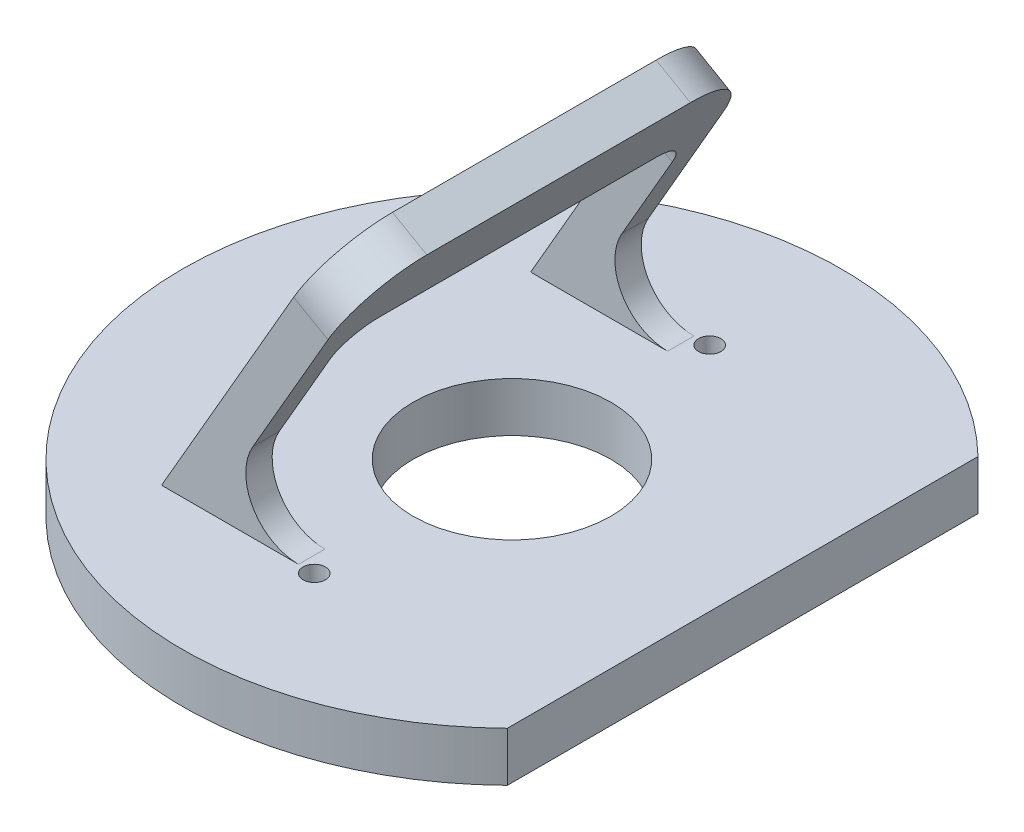
SolidWorks part; units mm, degrees
ref_plane "前视基准面" through (0, 0, 0) normal (0, 0, 1) x (1, 0, 0)
ref_plane "上视基准面" through (0, 0, 0) normal (0, 1, 0) x (1, 0, 0)
ref_plane "右视基准面" through (0, 0, 0) normal (1, 0, 0) x (0, 0, -1)
other "Configuration Table"
sketch "草图9" plane through (0, 0, 0) normal (0, 1, 0) x (1, 0, 0)
  line L0 (70, 71.4143) -> (70, -71.4143)
  arc A0 (70, 71.4143) -> (70, -71.4143) centre (0, 0) ccw
  circle A1 centre (0, 0) radius 30
  dimension "D1" = 200
  dimension "D2" = 60
  dimension "D3" = 70
extrude "凸台-拉伸3" add sketch "草图9" along normal blind 15
sketch "草图10" plane through (0, 0, 0) normal (0, 1, 0) x (1, 0, 0)
  line L0 (-55, 72.7753) -> (-55, -63.7573) construction
  dimension "D1" = 55
ref_plane "基准面1" through (-41.25, 23.8157, 0) normal (-0.866, 0.5, 0) x (0, 0, 1)
sketch "草图11" plane through (-41.25, 23.8157, 0) normal (-0.866, 0.5, 0) x (0, 0, 1)
  line L0 (-60, -9.9798) -> (-60, 70.0202)
  line L1 (0, -9.9798) -> (0, 116.3499) construction
  line L2 (-40, 90.0202) -> (40, 90.0202)
  line L3 (-52, -9.9798) -> (-52, 55.0202)
  line L4 (-42, 65.0202) -> (42, 65.0202)
  line L5 (-60, -9.9798) -> (-52, -9.9798)
  line L6 (-73.9369, -9.9798) -> (90.9367, -9.9798) construction
  line L7 (60, -9.9798) -> (52, -9.9798)
  line L8 (52, -9.9798) -> (52, 55.0202)
  line L9 (60, -9.9798) -> (60, 70.0202)
  arc A0 (-52, 55.0202) -> (-42, 65.0202) centre (-42, 55.0202) cw
  arc A1 (-60, 70.0202) -> (-40, 90.0202) centre (-40, 70.0202) cw
  arc A2 (60, 70.0202) -> (40, 90.0202) centre (40, 70.0202) ccw
  arc A3 (52, 55.0202) -> (42, 65.0202) centre (42, 55.0202) ccw
  point P13 (-52, 65.0202)
  point P16 (-60, 90.0202)
  point P18 (0, 65.0202)
  point P19 (0, 90.0202)
  point P25 (60, 90.0202)
  point P26 (52, 65.0202)
  dimension "D6" = 10
  dimension "D7" = 20
  dimension "D1" = 100
  dimension "D2" = 75
  dimension "D3" = 60
  dimension "D4" = 8
  dimension "D5" = 9.9798
extrude "凸台-拉伸4" add sketch "草图11" against normal blind 12
fillet "圆角2" radius 16 2 edges at (-32.4833, 15, -56) (-32.4833, 15, 56)
sketch "草图12" plane through (0, 0, 0) normal (0, 1, 0) x (1, 0, 0)
  line L0 (0, 0) -> (-117.4445, 0) construction
hole_wizard "M8 螺纹孔2" positions "草图13" profile "草图14" tap size "M8" standard "GB" end condition up to next
sketch "草图13" plane through (0, 15, 0) normal (0, 1, 0) x (1, 0, 0)
  line L0 (0, 0) -> (-117.4445, 0) construction
  point P0 (-60, 0)
  dimension "D1" = 60
sketch "草图14" plane through (-60, 15, 0) normal (1, 0, 0) x (0, 0, 1)
  line L0 (0, 0) -> (0, 15)
  line L1 (0, 15) -> (3.4, 15)
  line L2 (3.4, 15) -> (3.4, 0)
  line L5 (3.4, 0) -> (0, 0)
  line L11 (0, -6.35) -> (0, 107.95) construction
  dimension "通孔螺纹孔钻头直径" = 6.8
  dimension "通孔螺纹孔钻头深度" = 15
cosmetic thread "孔螺蚊线2" parameters "D2"=8
ref_axis "基准轴2" through (0, 0, 0) along (0, 1, 0)
pattern_circular "阵列(圆周)2" count 4 over 360 about axis through (0, 0, 0) along (0, 1, 0) skipping 2 of "M8 螺纹孔2"
